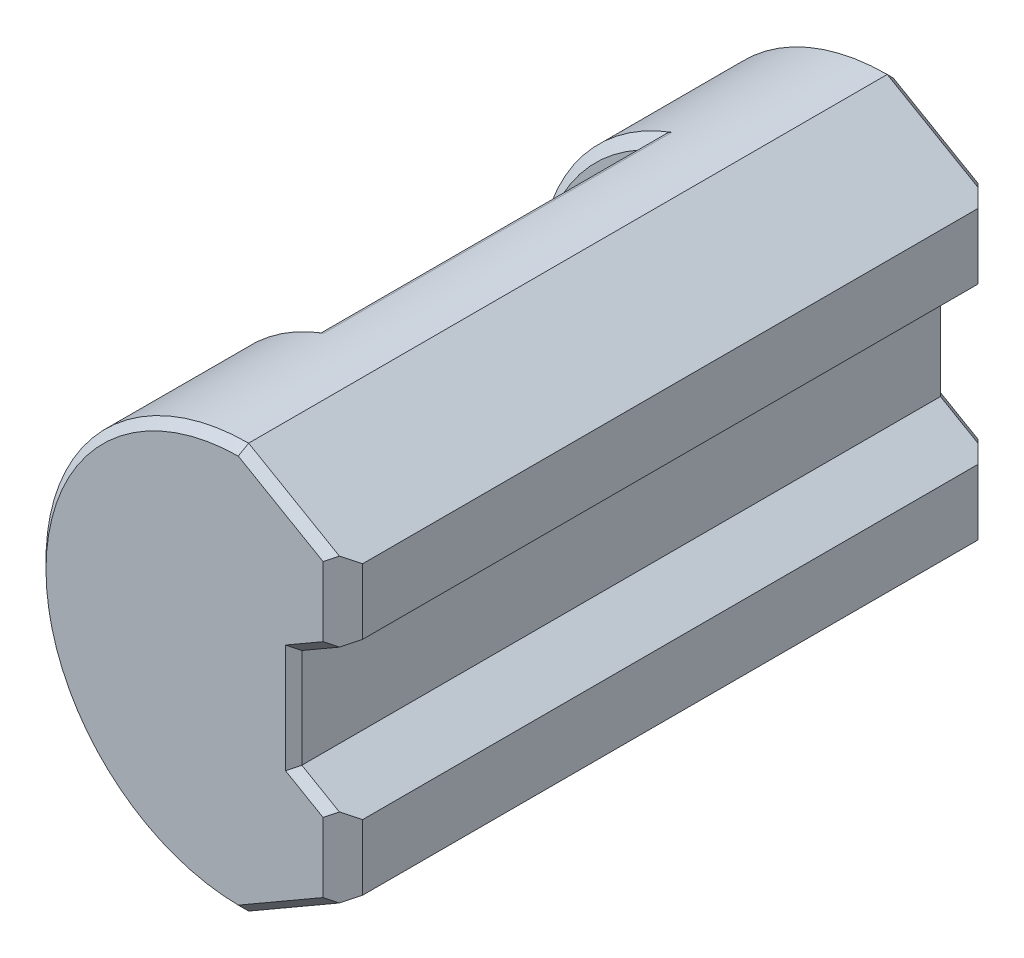
SolidWorks part; units mm, degrees
ref_plane "Front Plane" through (0, 0, 0) normal (0, 0, 1) x (1, 0, 0)
ref_plane "Top Plane" through (0, 0, 0) normal (0, 1, 0) x (1, 0, 0)
ref_plane "Right Plane" through (0, 0, 0) normal (1, 0, 0) x (0, 0, -1)
sketch "Sketch1" plane through (0, 0, 0) normal (0, 0, 1) x (1, 0, 0)
  line L0 (0, 4.95) -> (0, -4.95)
  arc A0 (0, 4.95) -> (0, -4.95) centre (0, 0) ccw
  dimension "D1" = 9.9
extrude "Boss-Extrude1" add sketch "Sketch1" along normal mid plane 16
ref_axis "Axis1" through (0, 0, -8.8) along (0, 0, 1)
sketch "Sketch4" plane through (0, 0, 0) normal (0, 0, 1) x (1, 0, 0)
  line L0 (0, 0) -> (0, -4.95) construction
  circle A0 centre (0, -2.475) radius 2.475
extrude "Cut-Extrude1" [suppressed] cut sketch "Sketch4" against normal through all both and the other way through all
ref_axis "Axis2" [suppressed] through (0, -5, -8) along (0, 0, 1)
ref_plane "Plane1" [suppressed] through (0, -5, 0) normal (0, 1, 0) x (1, 0, 0)
sketch "Sketch6" plane through (0, 0, 0) normal (0, 0, 1) x (1, 0, 0)
  line L0 (0, -4.95) -> (0, 4.95)
  line L1 (0, 0) -> (1.3, 0) construction
  line L2 (2.5, 1.9066) -> (2.5, -1.9066) construction
  line L3 (0, 4.95) -> (2.5, 3.5066)
  line L4 (2.5, 3.5066) -> (2.5, 1.9066)
  line L5 (2.5, 1.9066) -> (1.3, 1.2138)
  line L6 (1.3, 1.2138) -> (1.3, -1.2138)
  line L7 (1.3, -1.2138) -> (2.5, -1.9066)
  line L8 (2.5, -1.9066) -> (2.5, -3.5066)
  line L9 (2.5, -3.5066) -> (0, -4.95)
  line L10 (2.5, 1.9066) -> (2.5, -1.9066) construction
  arc A0 (0, 4.95) -> (0, -4.95) centre (0, 0) cw construction
  arc A1 (0, 4.95) -> (0, -4.95) centre (0, 0) ccw construction
  point P12 (2.5, 0)
  dimension "D1" = 1.3
  dimension "D3" = 60
  dimension "D2" = 2.5
  dimension "D4" = 60
  dimension "D5" = 1.6
extrude "Boss-Extrude2" add sketch "Sketch6" against normal up to surface and the other way up to surface up to face at (-2.475, 0, -8) other way up to face at (-2.475, 0, 8)
sketch "Sketch7" plane through (0, 0, 0) normal (0, 1, 0) x (1, 0, 0)
  line L0 (-4.95, 5.7) -> (-3.75, 5.7)
  line L1 (-4.95, 8) -> (-4.95, -8) construction
  line L2 (-3.75, 5.7) -> (-3.75, 6.5)
  line L3 (-3.75, 6.5) -> (-1.95, 6.5)
  line L4 (-1.95, 6.5) -> (-1.95, -6.5) construction
  line L5 (-1.95, -6.5) -> (-3.75, -6.5)
  line L6 (-3.75, -6.5) -> (-3.75, -5.7)
  line L7 (-3.75, -5.7) -> (-4.95, -5.7)
  line L8 (-4.95, -5.7) -> (-4.95, 5.7)
  line L9 (0, 0) -> (-4.95, 0) construction
  line L10 (-1.95, 5.7) -> (0.05, 5.7)
  line L11 (0.05, 5.7) -> (0.05, -5.7)
  line L13 (-1.95, 6.5) -> (-1.95, 5.7)
  line L14 (-1.95, -6.5) -> (-1.95, -5.7)
  line L15 (-1.95, -5.7) -> (0.05, -5.7)
  dimension "D1" = 1.2
  dimension "D2" = 1.8
  dimension "D3" = 0.8
  dimension "D4" = 13
  dimension "D5" = 11.4
  dimension "D6" = 2
revolve "Cut-Revolve1" [suppressed] cut sketch "Sketch7" angle 120 about axis through (0, 0, -8.8) along (0, 0, 1)
sketch "Sketch8" plane through (0, 0, 0) normal (0, 0, 1) x (1, 0, 0)
  line L0 (-2.83, 0) -> (0, 0) construction
  line L1 (-3.75, 0) -> (-4.95, 0) construction
  line L2 (-2.3182, 1.6232) -> (0, 0) construction
  line L3 (0, 0) -> (-2.3182, -1.6232) construction
  line L4 (-2.3182, 1.6232) -> (-3.2861, 2.3009) construction
  line L5 (-3.9816, -0.7523) -> (-4.9494, -0.0746) construction
  line L6 (-0.6548, 3.9988) -> (-1.6227, 4.6765) construction
  arc A0 (-2.3182, 1.6232) -> (-2.3182, -1.6232) centre (0, 0) ccw construction
  arc A1 (-3.0718, 2.1509) -> (-3.0718, -2.1509) centre (0, 0) ccw
  arc A2 (-1.5646, 1.0955) -> (-1.5646, -1.0955) centre (0, 0) ccw
  arc A3 (-1.5646, 1.0955) -> (-3.0718, 2.1509) centre (-2.3182, 1.6232) ccw
  arc A4 (-3.0718, -2.1509) -> (-1.5646, -1.0955) centre (-2.3182, -1.6232) ccw
  arc A5 (0, 4.95) -> (0, -4.95) centre (0, 0) ccw construction
  arc A7 (0, 4.95) -> (0, -4.95) centre (0, 0) ccw construction
  arc A8 (-3.9816, -0.7523) -> (-0.6548, 3.9988) centre (-2.3182, 1.6232) ccw construction
  arc A9 (-1.6227, 4.6765) -> (-4.9494, -0.0746) centre (-3.2861, 2.3009) ccw construction
  point P3 (-2.83, 0)
  point P13 (-2.8021, 1.9621)
  dimension "D1" = 0.92
  dimension "D4" = 2.9
  dimension "D2" = 1.2
  dimension "D3" = 35
  dimension "D5" = 2.83
extrude "Cut-Extrude2" cut sketch "Sketch8" against normal mid plane 14
sketch "Sketch10" [suppressed] plane through (0, 0, 0) normal (0, 0, 1) x (1, 0, 0)
  line L0 (0, -5) -> (-2.91, -5) construction
  line L1 (8.8, -5) -> (-8.8, -5) construction
  line L2 (-3.8, -5) -> (-5, -5) construction
  line L3 (-4.4396, -2.7) -> (-2.91, -2.7)
  line L4 (-2.91, -7.3) -> (-5, -7.3)
  line L5 (-5, -7.3) -> (-5, -2.7)
  line L6 (-5, -2.7) -> (-4.4396, -2.7)
  circle A0 centre (-2.91, -5) radius 0.89
  arc A1 (0, 0) -> (0, -10) centre (0, -5) ccw construction
  arc A2 (-2.91, -2.7) -> (-2.91, -7.3) centre (-2.91, -5) cw
  dimension "D1" = 1.78
  dimension "D3" = 2.3
  dimension "D2" = 1.2
  dimension "D4" = 2.09
extrude "Boss-Extrude3" [suppressed] add sketch "Sketch10" along normal mid plane 7.6
fillet "Fillet4" [suppressed] radius 0.4
sketch "Sketch9" plane through (0, 0, 0) normal (0, 0, 1) x (1, 0, 0)
  line L0 (-3.1298, -5.0603) -> (-0.9703, -3.5482)
  line L3 (0, 0) -> (-2.3182, -1.6232) construction
  line L5 (-1.91, 0) -> (-0.48, 0) construction
  line L6 (-0.48, 0) -> (-5.95, 0)
  arc A0 (-0.9703, -3.5482) -> (-0.3932, -0.2753) centre (-2.3182, -1.6232) ccw
  arc A1 (-1.5646, 1.0955) -> (-1.5646, -1.0955) centre (0, 0) ccw construction
  arc A2 (-3.0718, -2.1509) -> (-1.5646, -1.0955) centre (-2.3182, -1.6232) ccw construction
  arc A3 (-0.48, 0) -> (-0.3932, -0.2753) centre (0, 0) ccw
  arc A4 (-5.95, 0) -> (-3.1298, -5.0603) centre (0, 0) ccw
  arc A5 (0, 5.95) -> (0, -5.95) centre (0, 0) ccw
  arc A6 (0, 5.95) -> (0, -5.95) centre (0, 0) ccw construction
  dimension "D1" = 2.35
  dimension "D3" = 1
extrude "Cut-Extrude3" cut sketch "Sketch9" against normal mid plane 8
fillet "Fillet1" radius 0.3 1 edges at (-2.2208, -4.4239, 0)
mirror "Mirror2" [suppressed] about plane through (0, 0, 0) normal (0, 1, 0)
mirror "Mirror1" about plane through (0, 0, 0) normal (0, 1, 0) of "Cut-Extrude3", "Fillet1"
other "Move Face1" flip direction yes face at (-3.4109, 0, -5.5) face at (-2.0544, -2, -5.5) face at (-2.0544, 2, -5.5) face at (-1.7373, 0, -5.5) face at (-1.7373, 0, 5.5) face at (-2.0544, 2, 5.5) face at (-3.4109, 0, 5.5) face at (-2.0544, -2, 5.5) offset 0.1 parameters "D1"=0.1
chamfer "Chamfer4" distance 0.2 angle 45 16 edges at (1.25, 4.2283, 8) (2.5, 2.7066, 8) (1.9, 1.5602, 8) (1.3, 0, 8) (1.9, -1.5602, 8) (2.5, -2.7066, 8) (1.25, -4.2283, 8) (-4.95, 0, 8) (1.25, -4.2283, -8) (2.5, -2.7066, -8) (1.9, -1.5602, -8) (1.3, 0, -8) (1.9, 1.5602, -8) (2.5, 2.7066, -8) (1.25, 4.2283, -8) (-4.95, 0, -8)
chamfer "Chamfer1" distance 0.35 angle 45 8 edges at (-3.85, 0, -4) (-1.7332, 2.4588, -4) (-1.81, 0, -4) (-3.85, 0, 4) (-1.7332, 2.4588, 4) (-1.81, 0, 4) (-1.7332, -2.4588, -4) (-1.7332, -2.4588, 4)
chamfer "Chamfer2" distance 0.25 angle 45 2 edges at (-4.95, 0, -4) (-4.95, 0, 4)
sketch "Sketch13" [suppressed] plane through (0, 0, 0) normal (0, 0, 1) x (1, 0, 0)
  line L0 (10, -10) -> (10, 10)
  arc A0 (10, 10) -> (0, 0) centre (0, 10) ccw
  arc A1 (0, 0) -> (10, -10) centre (0, -10) ccw
  arc A2 (0, 0) -> (0, -20) centre (0, -10) ccw construction
  arc A3 (0, 20) -> (0, 0) centre (0, 10) ccw construction
extrude "Cut-Extrude4" [suppressed] cut sketch "Sketch13" against normal mid plane 4.2
sketch "Sketch14" plane through (0, 0, -7) normal (0, 0, -1) x (-1, 0, 0)
  circle A0 centre (2.3182, 1.6232) radius 0.9
  arc A1 (3.1537, 2.2083) -> (1.4827, 1.0382) centre (2.3182, 1.6232) ccw construction
  dimension "D1" = 1.8
extrude "Cut-Extrude5" cut sketch "Sketch14" along normal through all draft 10 draft outward yes
fillet "Fillet5" [suppressed] radius 1
sketch "Sketch15" [suppressed] plane through (0, 0, 0) normal (0, 0, 1) x (1, 0, 0)
  line L0 (-6.2912, 18.9848) -> (-5.7358, 18.1915)
  line L1 (0, 10) -> (0, 7.7212) construction
  line L2 (-5.7358, 18.1915) -> (0.3932, 18.1915)
  line L3 (0.3932, 18.1915) -> (0.3932, -18.1915)
  line L4 (0.3932, -18.1915) -> (-5.7358, -18.1915)
  line L5 (-5.7358, -18.1915) -> (-6.2912, -18.9848)
  line L6 (-6.2912, -18.9848) -> (-6.2912, -20)
  line L7 (-6.2912, -20) -> (3.9153, -20)
  line L8 (3.9153, -20) -> (3.9153, 20)
  line L9 (3.9153, 20) -> (-6.2912, 20)
  line L10 (-6.2912, 20) -> (-6.2912, 18.9848)
  arc A0 (0, 20) -> (0, -20) centre (0, 0) ccw construction
  arc A1 (0, 20) -> (-6.3897, 2.3077) centre (0, 10) ccw construction
  arc A2 (-6.3897, -2.3077) -> (0, -20) centre (0, -10) ccw construction
  dimension "D1" = 35
  dimension "D2" = 35
extrude "Cut-Extrude7" [suppressed] cut sketch "Sketch15" against normal through all both and the other way through all
sketch "Sketch16" [suppressed] plane through (0, 0, 0) normal (0, 0, 1) x (1, 0, 0)
  circle A0 centre (-7.91, 10) radius 1.15
  circle A1 centre (-7.91, -10) radius 1.15
  dimension "D1" = 2.3
extrude "Cut-Extrude8" [suppressed] cut sketch "Sketch16" against normal mid plane 10 draft 6
chamfer "Chamfer3" [suppressed] distance 0.3 angle 45
pattern_circular "CirPattern1" [suppressed] count 2 every 15 about axis through (0, 0, -8.8) along (0, 0, 1) of bodies 131
other "Move Face2" flip direction yes face at (2.4, -2.7066, 7.9) face at (2.4, 2.7066, 7.9) face at (2.4, -2.7066, -7.9) face at (2.4, 2.7066, -7.9) offset 0.2 parameters "D1"=0.2
